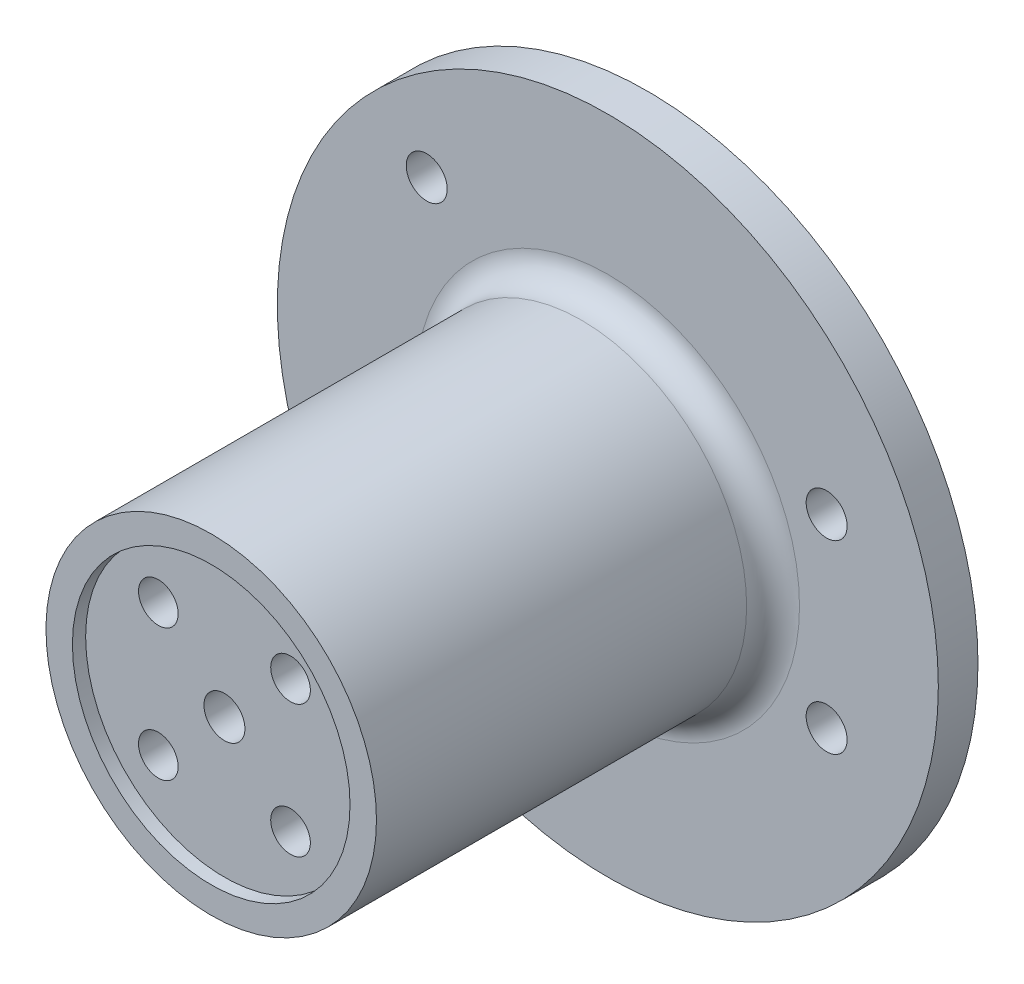
SolidWorks part; units mm, degrees
ref_plane "前视基准面" through (0, 0, 0) normal (0, 0, 1) x (1, 0, 0)
ref_plane "上视基准面" through (0, 0, 0) normal (0, 1, 0) x (1, 0, 0)
ref_plane "右视基准面" through (0, 0, 0) normal (1, 0, 0) x (0, 0, -1)
other "Configuration Table"
ref_plane "基准面1" through (0, 0, 0.0483) normal (0, 0, 1) x (1, 0, 0)
sketch "草图2" plane through (0, 0, 0.0483) normal (0, 0, 1) x (1, 0, 0)
  circle A0 centre (-1.0507, -17) radius 25
  circle A1 centre (-14.75, -3) radius 1.55
  circle A2 centre (-14.75, -17) radius 1.55
  circle A3 centre (-14.75, -31) radius 1.55
  circle A4 centre (15.5, -23.95) radius 1.55
  circle A5 centre (15.5, -9.95) radius 1.55
  dimension "D1" = 50
extrude "凸台-拉伸1" add sketch "草图2" along normal blind 3
sketch "草图3" plane through (0, 0, 3.0483) normal (0, 0, 1) x (1, 0, 0)
  circle A1 centre (-1.0507, -17) radius 12.5
extrude "凸台-拉伸2" add sketch "草图3" along normal blind 30
sketch "草图4" plane through (0, 0, 0.0483) normal (0, 0, -1) x (-1, 0, 0)
  line L1 (-3.9493, -12) -> (6.0507, -12)
  line L2 (-3.9493, -12) -> (-3.9493, -22)
  line L3 (-3.9493, -22) -> (6.0507, -22)
  line L4 (6.0507, -12) -> (6.0507, -22)
  line L5 (-3.9493, -12) -> (6.0507, -22) construction
  line L6 (-3.9493, -22) -> (6.0507, -12) construction
  circle A0 centre (1.0507, -17) radius 10.5
  circle A1 centre (1.0507, -17) radius 4
  circle A2 centre (6.0507, -12) radius 2.5
  circle A3 centre (6.0507, -22) radius 2.5
  circle A4 centre (-3.9493, -12) radius 2.5
  circle A5 centre (-3.9493, -22) radius 2.5
  dimension "D1" = 21
  dimension "D2" = 8
  dimension "D5" = 5
  dimension "D6" = 5
  dimension "D7" = 5
  dimension "D8" = 5
  dimension "D3" = 10
  dimension "D4" = 10
extrude "切除-拉伸1" cut sketch "草图4" against normal blind 18 contours L1 A2 L4 | L4 A2 L1 | L3 A3 L4 | L4 A3 L3 | L2 A5 L3 | L3 A5 L2 | L2 A4 L1 | L1 A4 L2 | A1 region at (4.303, -11.6463, 0.0483) region at (2.8882, -13.061, 0.0483) region at (-6.4044, -11.6463, 0.0483) region at (-4.9897, -13.061, 0.0483) region at (2.8882, -20.939, 0.0483) region at (4.303, -22.3537, 0.0483) region at (-6.4044, -22.3537, 0.0483) region at (-4.9897, -20.939, 0.0483) region at (-1.0507, -17, 0.0483)
sketch "草图5" plane through (0, 0, 0.0483) normal (0, 0, -1) x (-1, 0, 0)
  circle A0 centre (1.0507, -17) radius 2.467
  circle A1 centre (6.0507, -12) radius 1.5
  circle A2 centre (-3.9493, -12) radius 1.5
  circle A3 centre (-3.9493, -22) radius 1.5
  circle A4 centre (6.0507, -22) radius 1.5
  dimension "D1" = 3
  dimension "D2" = 3
  dimension "D3" = 3
  dimension "D4" = 3
extrude "切除-拉伸2" cut sketch "草图5" against normal blind 33
sketch "草图6" plane through (0, 0, 33.0483) normal (0, 0, 1) x (1, 0, 0)
  circle A0 centre (-1.0507, -17) radius 10.5
  dimension "D1" = 21
extrude "切除-拉伸3" cut sketch "草图6" against normal blind 1
fillet "圆角1" radius 2 1 edges at (11.4493, -17, 3.0483) type face fillet first side face at (11.4493, -17, 33.0483) second side face at (-2.4254, -17, 3.0483)
sketch "草图8" plane through (0, 0, 0.0483) normal (0, 0, -1) x (-1, 0, 0)
  circle A0 centre (1.0507, -17) radius 9.5711
extrude "凸台-拉伸4" add sketch "草图8" against normal blind 18
sketch "草图9" plane through (0, 0, 0.0483) normal (0, 0, -1) x (-1, 0, 0)
  line L1 (-3.9493, -22) -> (6.0507, -22)
  line L2 (-3.9493, -22) -> (-3.9493, -12)
  line L3 (-3.9493, -12) -> (6.0507, -12)
  line L4 (6.0507, -22) -> (6.0507, -12)
  line L5 (-3.9493, -22) -> (6.0507, -12) construction
  line L6 (-3.9493, -12) -> (6.0507, -22) construction
  circle A0 centre (1.0507, -17) radius 3.5
  circle A1 centre (-3.9493, -12) radius 3
  circle A2 centre (6.0507, -12) radius 3
  circle A3 centre (-3.9493, -22) radius 3
  circle A4 centre (6.0507, -22) radius 3
  dimension "D1" = 7
  dimension "D4" = 6
  dimension "D5" = 6
  dimension "D6" = 6
  dimension "D7" = 6
  dimension "D2" = 10
  dimension "D3" = 10
extrude "切除-拉伸7" cut sketch "草图9" against normal blind 20 contours L2 A1 L3 | L3 A1 L2 | A0 | A2 | A4 | A3 region at (4.3737, -11.5756, 0.0483) region at (2.676, -13.2732, 0.0483) region at (-1.0507, -17, 0.0483)
sketch "草图10" plane through (0, 0, 20.0483) normal (0, 0, -1) x (-1, 0, 0)
  circle A0 centre (1.0507, -17) radius 1.55
  circle A1 centre (1.0507, -17) radius 2.467
  dimension "D1" = 3.1
extrude "凸台-拉伸5" add sketch "草图10" against normal blind 12
